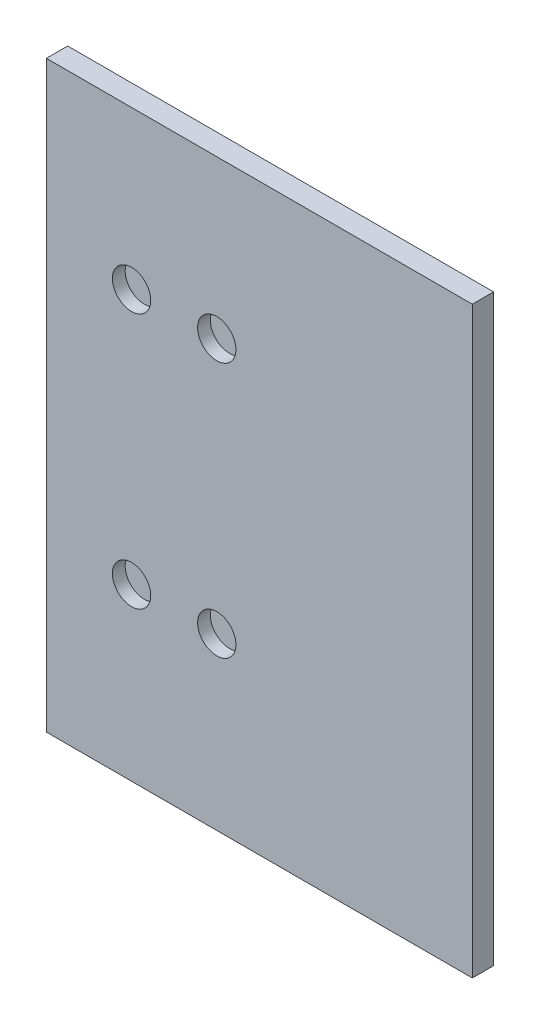
SolidWorks part; units mm, degrees
material "ABS"
ref_plane "Front Plane" through (0, 0, 0) normal (0, 0, 1) x (1, 0, 0)
ref_plane "Top Plane" through (0, 0, 0) normal (0, 1, 0) x (1, 0, 0)
ref_plane "Right Plane" through (0, 0, 0) normal (1, 0, 0) x (0, 0, -1)
sketch "Sketch1" plane through (0, 0, 0) normal (0, 0, 1) x (1, 0, 0)
  line L0 (0, 173.99) -> (63.5, 173.99)
  line L1 (0, 173.99) -> (-63.5, 173.99)
  line L7 (-63.5, 173.99) -> (-63.5, 0)
  line L8 (63.5, 173.99) -> (63.5, 0)
  line L9 (63.5, 0) -> (-63.5, 0)
extrude "Boss-Extrude1" add sketch "Sketch1" along normal blind 6.35
sketch "Sketch2" plane through (0, 0, 0) normal (0, 0, -1) x (-1, 0, 0)
  circle A0 centre (-48.26, 134.62) radius 5.715
  circle A1 centre (-7.62, 134.62) radius 5.715
  circle A2 centre (-48.26, 50.8) radius 5.715
  circle A3 centre (-7.62, 50.8) radius 5.715
sketch "Sketch3" plane through (0, 0, 6.35) normal (0, 0, 1) x (1, 0, 0)
  circle A0 centre (-38.1, 127) radius 5.715
  circle A1 centre (-12.7, 127) radius 5.715
  circle A2 centre (-38.1, 50.8) radius 5.715
  circle A3 centre (-12.7, 50.8) radius 5.715
  point P2 (0, 0)
extrude "Cut-Extrude1" cut sketch "Sketch3" against normal blind 3.81 contours A0 | A1 | A3 | A2
extrude "Cut-Extrude2" cut sketch "Sketch2" against normal blind 3.81 contours A0 | A1 | A3 | A2
